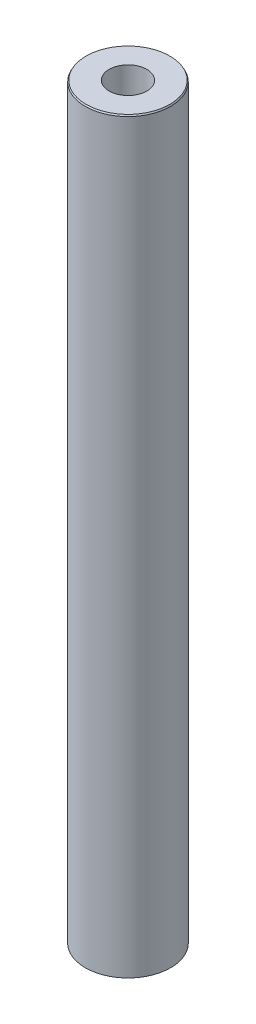
SolidWorks part; units mm, degrees
ref_plane "Front Plane" through (0, 0, 0) normal (0, 0, 1) x (1, 0, 0)
ref_plane "Top Plane" through (0, 0, 0) normal (0, 1, 0) x (1, 0, 0)
ref_plane "Right Plane" through (0, 0, 0) normal (1, 0, 0) x (0, 0, -1)
sketch "Sketch1" plane through (0, 0, 0) normal (0, 1, 0) x (1, 0, 0)
  circle A0 centre (0, 0) radius 10
  dimension "SHAFT_OD" = 20
extrude "Boss-Extrude1" add sketch "Sketch1" along normal blind 175.3285
sketch "Sketch2" plane through (0, 0, 0) normal (0, 1, 0) x (1, 0, 0)
  circle A0 centre (0, 0) radius 4.4139
  dimension "BORE_D" = 8.8279
extrude "Cut-Extrude1" cut sketch "Sketch2" along normal through all
chamfer "Chamfer1" distance 0.3233 angle 30 2 edges at (0, 175.3285, 10) (0, 0, 10) first distance on face at (0, 175.3285, 10) first distance on face at (0, 0, 4.4139)
